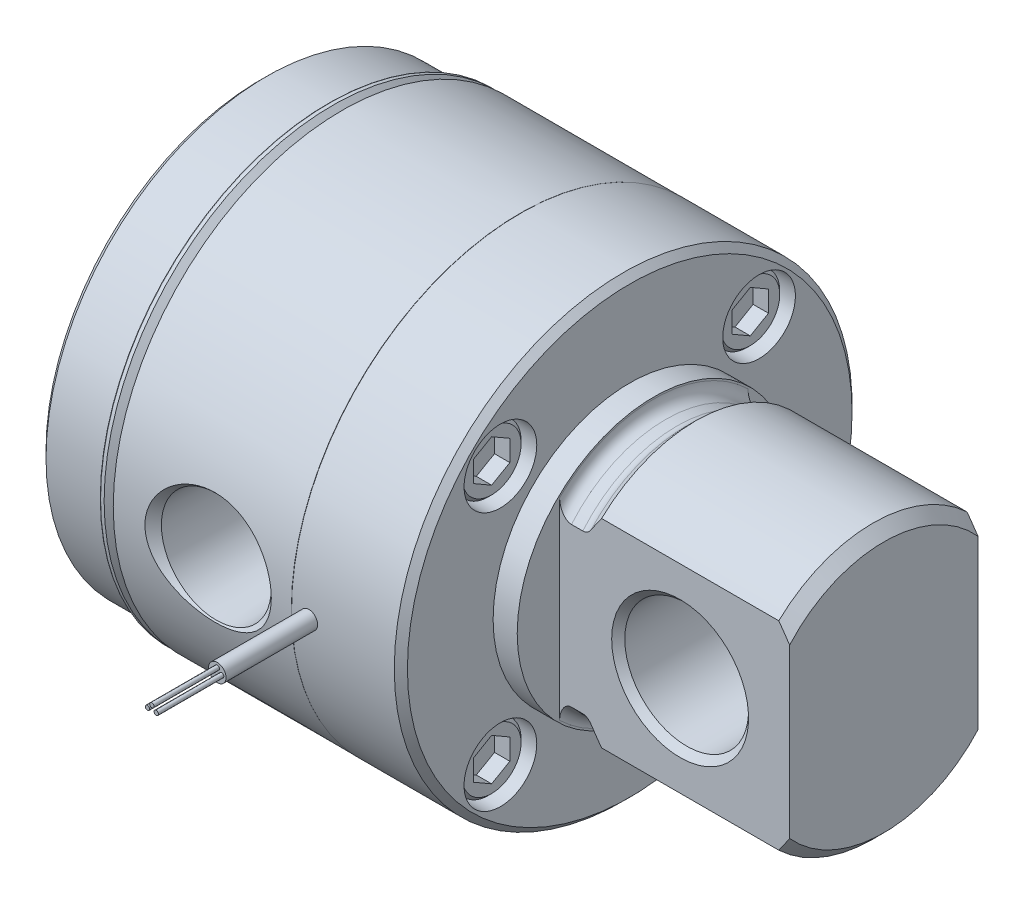
SolidWorks part; units mm, degrees
ref_plane "Front Plane" through (0, 0, 0) normal (0, 0, 1) x (1, 0, 0)
ref_plane "Top Plane" through (0, 0, 0) normal (0, 1, 0) x (1, 0, 0)
ref_plane "Right Plane" through (0, 0, 0) normal (1, 0, 0) x (0, 0, -1)
ref_plane "Plane1" through (0, 0, 0) normal (1, 0, 0) x (0, 0, -1)
sketch "Sketch1" plane through (0, 0, 0) normal (0, 0, 1) x (1, 0, 0)
  line L0 (-42.8752, 0) -> (-42.8752, 24.8158)
  line L1 (-42.8752, 24.8158) -> (-42.1132, 25.5778)
  line L2 (-42.1132, 25.5778) -> (-35.4838, 25.5778)
  line L3 (-35.4838, 25.5778) -> (-34.417, 24.511)
  line L4 (-34.417, 24.511) -> (-33.3502, 24.511)
  line L5 (-33.3502, 24.511) -> (-33.3502, 26.543)
  line L6 (-33.3502, 26.543) -> (-12.7127, 26.5303)
  line L7 (-12.7127, 26.5303) -> (-12.6746, 26.543)
  line L8 (-12.6746, 26.543) -> (-0.762, 26.543)
  line L9 (-0.762, 26.543) -> (0, 25.781)
  line L10 (0, 25.781) -> (0, 0)
  line L11 (0, 0) -> (-42.8752, 0)
  line L12 (0, 0) -> (-42.8752, 0) construction
revolve "Revolve1" add sketch "Sketch1" angle 360 about L12 reverse direction yes
sketch "Sketch2" plane through (0, 0, 0) normal (0, 0, 1) x (1, 0, 0)
  line L0 (-34.9316, 26.3188) -> (-32.8006, 24.1877)
  line L1 (-32.8006, 24.1877) -> (-32.4773, 24.511)
  line L2 (-32.4773, 24.511) -> (-34.4585, 26.4922)
  line L3 (-34.4585, 26.4922) -> (-34.8598, 26.4922)
  line L4 (-34.4585, 0) -> (-35.105, 0) construction
  arc A0 (-34.8598, 26.4922) -> (-34.9316, 26.3188) centre (-34.8598, 26.3906) ccw
revolve "Revolve2" add sketch "Sketch2" angle 360 about L4 reverse direction yes
ref_plane "Plane2" through (0, 0, 0) normal (1, 0, 0) x (0, 0, -1)
hole_wizard "Hole1" positions "Sketch4" profile "Sketch3" legacy
sketch "Sketch4" plane through (0, 0, 0) normal (1, 0, 0) x (0, 0, -1)
  point P0 (-14.997, 14.997)
sketch "Sketch3" plane through (0, 14.997, 14.997) normal (0, 1, 0) x (0, 0, -1)
  line L0 (0, 0) -> (0, 5.08)
  line L1 (0, 5.08) -> (4.2164, 5.08)
  line L2 (4.2164, 5.08) -> (4.2164, 0)
  line L3 (4.2164, 0) -> (0, 0)
  line L4 (0, 110) -> (0, -10) construction
  dimension "Diameter" = 8.4328
  dimension "Depth" = 5.08
sketch "Sketch5" plane through (0, 0, 0) normal (1, 0, 0) x (0, 0, -1)
  line L0 (-14.997, 14.997) -> (14.997, 14.997)
  line L1 (-14.997, 14.997) -> (-14.997, -14.997)
pattern_linear "LPattern1" count 2 spacing 29.9941 along (0, 0, -1) count 2 spacing 29.9941 along (0, -1, 0) of "Hole1"
ref_plane "Plane3" through (0, 0, 0) normal (0, -0.7071, 0.7071) x (1, 0, 0)
sketch "Sketch6" plane through (0, 0, 0) normal (0, -0.7071, 0.7071) x (1, 0, 0)
  line L0 (-5.08, 21.209) -> (-5.08, 25.0038)
  line L1 (-5.08, 25.0038) -> (-1.397, 25.0038)
  line L2 (-1.397, 25.0038) -> (-1.016, 24.6228)
  line L3 (-1.016, 24.6228) -> (-1.016, 21.209)
  line L4 (-1.016, 21.209) -> (-5.08, 21.209)
  line L5 (-1.016, 21.209) -> (-5.08, 21.209) construction
revolve "Revolve3" add sketch "Sketch6" angle 360 about L5 reverse direction yes
sketch "Sketch7" plane through (0, 0, 0) normal (1, 0, 0) x (0, 0, -1)
  line L0 (-14.997, 14.997) -> (14.997, 14.997)
  line L1 (-14.997, 14.997) -> (-14.997, -14.997)
pattern_linear "LPattern2" count 2 spacing 29.9941 along (0, 0, -1) count 2 spacing 29.9941 along (0, -1, 0) of "Revolve3"
ref_plane "Plane4" through (-1.016, 0, 0) normal (1, 0, 0) x (0, 0, -1)
sketch "Sketch8" plane through (-1.016, 0, 0) normal (1, 0, 0) x (0, 0, -1)
  line L0 (-17.1052, 16.2142) -> (-17.1052, 13.7799)
  line L1 (-17.1052, 13.7799) -> (-14.997, 12.5627)
  line L2 (-14.997, 12.5627) -> (-12.8888, 13.7799)
  line L3 (-12.8888, 13.7799) -> (-12.8888, 16.2142)
  line L4 (-12.8888, 16.2142) -> (-14.997, 17.4314)
  line L5 (-14.997, 17.4314) -> (-17.1052, 16.2142)
extrude "Cut-Extrude1" cut sketch "Sketch8" against normal blind 1.778
sketch "Sketch9" plane through (-1.016, 0, 0) normal (1, 0, 0) x (0, 0, -1)
  line L0 (-14.997, 14.997) -> (14.997, 14.997)
  line L1 (-14.997, 14.997) -> (-14.997, -14.997)
pattern_linear "LPattern3" count 2 spacing 29.9941 along (0, 0, -1) count 2 spacing 29.9941 along (0, -1, 0) of "Cut-Extrude1"
sketch "Sketch10" plane through (0, 0, 0) normal (0, 1, 0) x (1, 0, 0)
  line L0 (-10.668, -23.8887) -> (-9.652, -23.8887)
  line L1 (-9.652, -23.8887) -> (-9.652, -37.1602)
  line L2 (-9.652, -37.1602) -> (-10.668, -37.1602)
  line L3 (-10.668, -37.1602) -> (-10.668, -23.8887)
  line L4 (-10.668, -37.1602) -> (-10.668, -23.8887) construction
ref_plane "Plane5" through (0, 0, 24.6634) normal (0, 0, 1) x (1, 0, 0)
revolve "Revolve4" add sketch "Sketch10" angle 360 about L4 reverse direction yes
sketch "Sketch11" plane through (0, 0, 0) normal (0, 1, 0) x (1, 0, 0)
  line L0 (-11.176, -37.1602) -> (-10.922, -37.1602)
  line L1 (-10.922, -37.1602) -> (-10.922, -44.7439)
  line L2 (-10.922, -44.7439) -> (-11.176, -44.7439)
  line L3 (-11.176, -44.7439) -> (-11.176, -37.1602)
  line L4 (-11.176, -44.7439) -> (-11.176, -37.1602) construction
revolve "Revolve5" add sketch "Sketch11" angle 360 about L4 reverse direction yes
sketch "Sketch12" plane through (0, 0, 0) normal (0, 1, 0) x (1, 0, 0)
  line L0 (-10.16, -37.1602) -> (-9.906, -37.1602)
  line L1 (-9.906, -37.1602) -> (-9.906, -44.7439)
  line L2 (-9.906, -44.7439) -> (-10.16, -44.7439)
  line L3 (-10.16, -44.7439) -> (-10.16, -37.1602)
  line L4 (-10.16, -44.7439) -> (-10.16, -37.1602) construction
revolve "Revolve6" add sketch "Sketch12" angle 360 about L4 reverse direction yes
ref_plane "Plane6" through (-10.668, 0, 0) normal (1, 0, 0) x (0, 0, -1)
sketch "Sketch13" plane through (-10.668, 0, 0) normal (1, 0, 0) x (0, 0, -1)
  line L0 (-44.7439, 0.508) -> (-44.7439, 0.762)
  line L1 (-44.7439, 0.762) -> (-37.1602, 0.762)
  line L2 (-37.1602, 0.762) -> (-37.1602, 0.508)
  line L3 (-37.1602, 0.508) -> (-44.7439, 0.508)
  line L4 (-37.1602, 0.508) -> (-44.7439, 0.508) construction
revolve "Revolve7" add sketch "Sketch13" angle 360 about L4 reverse direction yes
sketch "Sketch14" plane through (0, 0, 0) normal (0, 0, 1) x (1, 0, 0)
  line L0 (-42.8752, 0) -> (-42.8752, 13.1699)
  line L1 (-42.8752, 13.1699) -> (-33.7058, 13.1699)
  line L2 (-33.7058, 13.1699) -> (-33.7058, 3.81)
  line L3 (-33.7058, 3.81) -> (-12.7, 3.81)
  line L4 (-12.7, 3.81) -> (-12.7, 12.7)
  line L5 (-12.7, 12.7) -> (-5.08, 12.7)
  line L6 (-5.08, 12.7) -> (-5.08, 0)
  line L7 (-5.08, 0) -> (-42.8752, 0)
  line L8 (-5.08, 0) -> (-42.8752, 0) construction
revolve "Cut-Revolve1" cut sketch "Sketch14" angle 360 about L8 reverse direction yes
sketch "Sketch15" plane through (0, 0, 0) normal (0, 1, 0) x (1, 0, 0)
  line L0 (-22.352, 0) -> (-16.6716, -3.2796)
  line L1 (-16.6716, -3.2796) -> (-16.6716, -3.429)
  line L2 (-16.6716, -3.429) -> (-15.9799, -25.5856)
  line L3 (-15.9799, -25.5856) -> (-15.0225, -26.543)
  line L4 (-15.0225, -26.543) -> (-22.352, -26.543)
  line L5 (-22.352, -26.543) -> (-22.352, 0)
  line L6 (-22.352, -26.543) -> (-22.352, 0) construction
revolve "Cut-Revolve2" cut sketch "Sketch15" angle 360 about L6 reverse direction yes
cosmetic thread "Cosmetic Thread1" parameters "D1"=20.574, "D2"=40.1763
sketch "Sketch16" plane through (0, 0, 0) normal (0, 0, 1) x (1, 0, 0)
  line L0 (0, 0) -> (0, 15.8432)
  line L1 (0, 15.8432) -> (2.794, 15.8432)
  line L2 (2.794, 15.8432) -> (2.794, 15.6337)
  line L3 (4.1656, 14.2621) -> (5.4771, 14.2621)
  line L4 (6.4469, 14.6638) -> (7.6581, 15.875)
  line L5 (7.6581, 15.875) -> (28.2042, 15.875)
  line L6 (28.2042, 15.875) -> (29.464, 14.6152)
  line L7 (29.464, 14.6152) -> (29.464, 0)
  line L8 (29.464, 0) -> (0, 0)
  line L9 (29.464, 0) -> (0, 0) construction
  arc A0 (2.794, 15.6337) -> (4.1656, 14.2621) centre (4.1656, 15.6337) ccw
  arc A1 (5.4771, 14.2621) -> (6.4469, 14.6638) centre (5.4771, 15.6337) ccw
revolve "Revolve8" add sketch "Sketch16" angle 360 about L9 reverse direction yes
cosmetic thread "Cosmetic Thread2" parameters "D1"=23.0171, "D2"=29.2303
ref_plane "Plane7" through (2.794, 0, 0) normal (1, 0, 0) x (0, 0, -1)
sketch "Sketch17" plane through (2.794, 0, 0) normal (1, 0, 0) x (0, 0, -1)
  line L0 (-26.543, -53.086) -> (26.543, -53.086)
  line L1 (26.543, -53.086) -> (26.543, 53.086)
  line L2 (26.543, 53.086) -> (-26.543, 53.086)
  line L3 (-26.543, 53.086) -> (-26.543, -53.086)
  line L4 (-10.922, -26.543) -> (10.922, -26.543)
  line L5 (10.922, -26.543) -> (10.922, 26.543)
  line L6 (10.922, 26.543) -> (-10.922, 26.543)
  line L7 (-10.922, 26.543) -> (-10.922, -26.543)
extrude "Cut-Extrude2" cut sketch "Sketch17" along normal blind 29.464
sketch "Sketch18" plane through (0, 0, 0) normal (0, 1, 0) x (1, 0, 0)
  line L0 (16.764, 10.922) -> (24.7015, 10.922)
  line L1 (24.7015, 10.922) -> (23.9395, 10.16)
  line L2 (23.9395, 10.16) -> (23.9395, -10.16)
  line L3 (23.9395, -10.16) -> (24.7015, -10.922)
  line L4 (24.7015, -10.922) -> (16.764, -10.922)
  line L5 (16.764, -10.922) -> (16.764, 10.922)
  line L6 (16.764, -10.922) -> (16.764, 10.922) construction
revolve "Cut-Revolve3" cut sketch "Sketch18" angle 360 about L6 reverse direction yes
ref_plane "Plane8" through (-42.8752, 0, 0) normal (1, 0, 0) x (0, 0, -1)
ref_plane "Plane9" through (0, 0, 0) normal (0, 0, 1) x (1, 0, 0)
ref_plane "Plane10" through (0, 0, 0) normal (0, 0, 1) x (1, 0, 0)
ref_plane "Plane11" through (0, 0, 0) normal (1, 0, 0) x (0, 0, -1)
ref_plane "Plane12" through (0, 0, 33.655) normal (0, 0, 1) x (1, 0, 0)
ref_plane "Plane13" through (0, -26.543, 0) normal (0, 1, 0) x (1, 0, 0)
ref_plane "IP1 XY" through (0, 0, 0) normal (1, 0, 0) x (0, 0, -1)
ref_plane "IP1 XZ" through (0, 0, 0) normal (0, -1, 0) x (-1, 0, 0)
ref_plane "IP1 YZ" through (0, 0, 0) normal (0, 0, -1) x (-1, 0, 0)
ref_axis "IP1 X" through (0, 0, 80.9) along (0, 0, -1)
ref_axis "IP1 Y" through (0, -50, 0) along (0, 1, 0)
ref_axis "IP1 Z" through (80.9, 0, 0) along (-1, 0, 0)
sketch3d "IP1"
  point P0 (0, 0, 0)
ref_plane "a+stroke XY" through (0, 0, 0) normal (0, 0, 1) x (1, 0, 0)
ref_plane "a+stroke XZ" through (0, 0, 0) normal (0, -1, 0) x (-1, 0, 0)
ref_plane "a+stroke YZ" through (0, 0, 0) normal (1, 0, 0) x (0, 0, -1)
ref_axis "a+stroke X" through (-80.9, 0, 0) along (1, 0, 0)
ref_axis "a+stroke Y" through (0, -50, 0) along (0, 1, 0)
ref_axis "a+stroke Z" through (0, 0, 80.9) along (0, 0, -1)
sketch3d "a+stroke"
  point P0 (0, 0, 0)
ref_plane "d1 XY" through (0, 0, 0) normal (1, 0, 0) x (0, 0, -1)
ref_plane "d1 XZ" through (0, 0, 0) normal (0, -1, 0) x (-1, 0, 0)
ref_plane "d1 YZ" through (0, 0, 26.543) normal (0, 0, -1) x (-1, 0, 0)
ref_axis "d1 X" through (0, 0, 80.9) along (0, 0, -1)
ref_axis "d1 Y" through (0, -50, 26.543) along (0, 1, 0)
ref_axis "d1 Z" through (80.9, 0, 26.543) along (-1, 0, 0)
sketch3d "d1"
  point P0 (0, 0, 26.543)
ref_plane "d2 XY" through (0, 0, 0) normal (1, 0, 0) x (0, 0, -1)
ref_plane "d2 XZ" through (0, 0, 0) normal (0, -1, 0) x (-1, 0, 0)
ref_plane "d2 YZ" through (0, 0, -26.543) normal (0, 0, -1) x (-1, 0, 0)
ref_axis "d2 X" through (0, 0, 80.9) along (0, 0, -1)
ref_axis "d2 Y" through (0, -50, -26.543) along (0, 1, 0)
ref_axis "d2 Z" through (80.9, 0, -26.543) along (-1, 0, 0)
sketch3d "d2"
  point P0 (0, 0, -26.543)
ref_plane "ff1 XY" through (0, 0, 0) normal (1, 0, 0) x (0, 0, -1)
ref_plane "ff1 XZ" through (0, 0, 0) normal (0, -1, 0) x (-1, 0, 0)
ref_plane "ff1 YZ" through (0, 0, 26.543) normal (0, 0, -1) x (-1, 0, 0)
ref_axis "ff1 X" through (0, 0, 80.9) along (0, 0, -1)
ref_axis "ff1 Y" through (0, -50, 26.543) along (0, 1, 0)
ref_axis "ff1 Z" through (80.9, 0, 26.543) along (-1, 0, 0)
sketch3d "ff1"
  point P0 (0, 0, 26.543)
ref_plane "ff2 XY" through (0, 0, 0) normal (1, 0, 0) x (0, 0, -1)
ref_plane "ff2 XZ" through (0, 0, 0) normal (0, -1, 0) x (-1, 0, 0)
ref_plane "ff2 YZ" through (0, 0, 36.195) normal (0, 0, -1) x (-1, 0, 0)
ref_axis "ff2 X" through (0, 0, 80.9) along (0, 0, -1)
ref_axis "ff2 Y" through (0, -50, 36.195) along (0, 1, 0)
ref_axis "ff2 Z" through (80.9, 0, 36.195) along (-1, 0, 0)
sketch3d "ff2"
  point P0 (0, 0, 36.195)
ref_plane "h1 XY" through (0, 0, 0) normal (0, 0, 1) x (1, 0, 0)
ref_plane "h1 XZ" through (0, 0, 0) normal (0, -1, 0) x (-1, 0, 0)
ref_plane "h1 YZ" through (2.794, 0, 0) normal (1, 0, 0) x (0, 0, -1)
ref_axis "h1 X" through (-80.9, 0, 0) along (1, 0, 0)
ref_axis "h1 Y" through (2.794, -50, 0) along (0, 1, 0)
ref_axis "h1 Z" through (2.794, 0, 80.9) along (0, 0, -1)
sketch3d "h1"
  point P0 (2.794, 0, 0)
ref_plane "k1 XY" through (0, 0, 0) normal (0, 0, 1) x (1, 0, 0)
ref_plane "k1 XZ" through (0, 15.875, 0) normal (0, -1, 0) x (-1, 0, 0)
ref_plane "k1 YZ" through (29.464, 0, 0) normal (1, 0, 0) x (0, 0, -1)
ref_axis "k1 X" through (-80.9, 15.875, 0) along (1, 0, 0)
ref_axis "k1 Y" through (29.464, -50, 0) along (0, 1, 0)
ref_axis "k1 Z" through (29.464, 15.875, 80.9) along (0, 0, -1)
sketch3d "k1"
  point P0 (29.464, 15.875, 0)
ref_plane "k2 XY" through (0, 0, 0) normal (0, 0, 1) x (1, 0, 0)
ref_plane "k2 XZ" through (0, -15.875, 0) normal (0, -1, 0) x (-1, 0, 0)
ref_plane "k2 YZ" through (29.464, 0, 0) normal (1, 0, 0) x (0, 0, -1)
ref_axis "k2 X" through (-80.9, -15.875, 0) along (1, 0, 0)
ref_axis "k2 Y" through (29.464, -50, 0) along (0, 1, 0)
ref_axis "k2 Z" through (29.464, -15.875, 80.9) along (0, 0, -1)
sketch3d "k2"
  point P0 (29.464, -15.875, 0)
ref_plane "l1 XY" through (0, 0, 0) normal (0, 0, 1) x (1, 0, 0)
ref_plane "l1 XZ" through (0, 15.8432, 0) normal (0, -1, 0) x (-1, 0, 0)
ref_plane "l1 YZ" through (2.794, 0, 0) normal (1, 0, 0) x (0, 0, -1)
ref_axis "l1 X" through (-80.9, 15.8432, 0) along (1, 0, 0)
ref_axis "l1 Y" through (2.794, -50, 0) along (0, 1, 0)
ref_axis "l1 Z" through (2.794, 15.8432, 80.9) along (0, 0, -1)
sketch3d "l1"
  point P0 (2.794, 15.8432, 0)
ref_plane "l2 XY" through (0, 0, 0) normal (0, 0, 1) x (1, 0, 0)
ref_plane "l2 XZ" through (0, -15.8432, 0) normal (0, -1, 0) x (-1, 0, 0)
ref_plane "l2 YZ" through (2.794, 0, 0) normal (1, 0, 0) x (0, 0, -1)
ref_axis "l2 X" through (-80.9, -15.8432, 0) along (1, 0, 0)
ref_axis "l2 Y" through (2.794, -50, 0) along (0, 1, 0)
ref_axis "l2 Z" through (2.794, -15.8432, 80.9) along (0, 0, -1)
sketch3d "l2"
  point P0 (2.794, -15.8432, 0)
ref_plane "n1 XY" through (0, 0, 0) normal (0, 0, 1) x (1, 0, 0)
ref_plane "n1 XZ" through (0, 0, 0) normal (0, -1, 0) x (-1, 0, 0)
ref_plane "n1 YZ" through (-10.668, 0, 0) normal (1, 0, 0) x (0, 0, -1)
ref_axis "n1 X" through (-80.9, 0, 0) along (1, 0, 0)
ref_axis "n1 Y" through (-10.668, -50, 0) along (0, 1, 0)
ref_axis "n1 Z" through (-10.668, 0, 80.9) along (0, 0, -1)
sketch3d "n1"
  point P0 (-10.668, 0, 0)
ref_plane "o1 XY" through (0, 0, 0) normal (0, 0, 1) x (1, 0, 0)
ref_plane "o1 XZ" through (0, 0, 0) normal (0, -1, 0) x (-1, 0, 0)
ref_plane "o1 YZ" through (-12.7, 0, 0) normal (1, 0, 0) x (0, 0, -1)
ref_axis "o1 X" through (-80.9, 0, 0) along (1, 0, 0)
ref_axis "o1 Y" through (-12.7, -50, 0) along (0, 1, 0)
ref_axis "o1 Z" through (-12.7, 0, 80.9) along (0, 0, -1)
sketch3d "o1"
  point P0 (-12.7, 0, 0)
ref_plane "o2 XY" through (0, 0, 0) normal (0, 0, 1) x (1, 0, 0)
ref_plane "o2 XZ" through (0, 0, 0) normal (0, -1, 0) x (-1, 0, 0)
ref_plane "o2 YZ" through (0, 0, 0) normal (1, 0, 0) x (0, 0, -1)
ref_axis "o2 X" through (-80.9, 0, 0) along (1, 0, 0)
ref_axis "o2 Y" through (0, -50, 0) along (0, 1, 0)
ref_axis "o2 Z" through (0, 0, 80.9) along (0, 0, -1)
sketch3d "o2"
  point P0 (0, 0, 0)
ref_plane "p1 XY" through (0, 0, 0) normal (0, 0, 1) x (1, 0, 0)
ref_plane "p1 XZ" through (0, 0, 0) normal (0, -1, 0) x (-1, 0, 0)
ref_plane "p1 YZ" through (-22.352, 0, 0) normal (1, 0, 0) x (0, 0, -1)
ref_axis "p1 X" through (-80.9, 0, 0) along (1, 0, 0)
ref_axis "p1 Y" through (-22.352, -50, 0) along (0, 1, 0)
ref_axis "p1 Z" through (-22.352, 0, 80.9) along (0, 0, -1)
sketch3d "p1"
  point P0 (-22.352, 0, 0)
ref_plane "q1 XY" through (2.794, 0, 0) normal (1, 0, 0) x (0, 0, -1)
ref_plane "q1 XZ" through (0, 0, 0) normal (0, -1, 0) x (-1, 0, 0)
ref_plane "q1 YZ" through (0, 0, 10.922) normal (0, 0, -1) x (-1, 0, 0)
ref_axis "q1 X" through (2.794, 0, 80.9) along (0, 0, -1)
ref_axis "q1 Y" through (2.794, -50, 10.922) along (0, 1, 0)
ref_axis "q1 Z" through (80.9, 0, 10.922) along (-1, 0, 0)
sketch3d "q1"
  point P0 (2.794, 0, 10.922)
ref_plane "q2 XY" through (2.794, 0, 0) normal (1, 0, 0) x (0, 0, -1)
ref_plane "q2 XZ" through (0, 0, 0) normal (0, -1, 0) x (-1, 0, 0)
ref_plane "q2 YZ" through (0, 0, -10.922) normal (0, 0, -1) x (-1, 0, 0)
ref_axis "q2 X" through (2.794, 0, 80.9) along (0, 0, -1)
ref_axis "q2 Y" through (2.794, -50, -10.922) along (0, 1, 0)
ref_axis "q2 Z" through (80.9, 0, -10.922) along (-1, 0, 0)
sketch3d "q2"
  point P0 (2.794, 0, -10.922)
ref_plane "r1 XY" through (0, 0, 0) normal (1, 0, 0) x (0, 0, -1)
ref_plane "r1 XZ" through (0, -14.997, 0) normal (0, -1, 0) x (-1, 0, 0)
ref_plane "r1 YZ" through (0, 0, 14.997) normal (0, 0, -1) x (-1, 0, 0)
ref_axis "r1 X" through (0, -14.997, 80.9) along (0, 0, -1)
ref_axis "r1 Y" through (0, -50, 14.997) along (0, 1, 0)
ref_axis "r1 Z" through (80.9, -14.997, 14.997) along (-1, 0, 0)
sketch3d "r1"
  point P0 (0, -14.997, 14.997)
ref_plane "r2 XY" through (0, 0, 0) normal (1, 0, 0) x (0, 0, -1)
ref_plane "r2 XZ" through (0, 14.997, 0) normal (0, -1, 0) x (-1, 0, 0)
ref_plane "r2 YZ" through (0, 0, -14.997) normal (0, 0, -1) x (-1, 0, 0)
ref_axis "r2 X" through (0, 14.997, 80.9) along (0, 0, -1)
ref_axis "r2 Y" through (0, -50, -14.997) along (0, 1, 0)
ref_axis "r2 Z" through (80.9, 14.997, -14.997) along (-1, 0, 0)
sketch3d "r2"
  point P0 (0, 14.997, -14.997)
ref_plane "s1 XY" through (0, 0, 0) normal (0, 0, 1) x (1, 0, 0)
ref_plane "s1 XZ" through (0, 0, 0) normal (0, -1, 0) x (-1, 0, 0)
ref_plane "s1 YZ" through (16.764, 0, 0) normal (1, 0, 0) x (0, 0, -1)
ref_axis "s1 X" through (-80.9, 0, 0) along (1, 0, 0)
ref_axis "s1 Y" through (16.764, -50, 0) along (0, 1, 0)
ref_axis "s1 Z" through (16.764, 0, 80.9) along (0, 0, -1)
sketch3d "s1"
  point P0 (16.764, 0, 0)
ref_plane "to_PCS XY" through (0, -26.543, 0) normal (0, -1, 0) x (-1, 0, 0)
ref_plane "to_PCS XZ" through (0, 0, 0) normal (0, 0, -1) x (-1, 0, 0)
ref_plane "to_PCS YZ" through (178.816, 0, 0) normal (1, 0, 0) x (0, 0, -1)
ref_axis "to_PCS X" through (-80.9, -26.543, 0) along (1, 0, 0)
ref_axis "to_PCS Y" through (178.816, -26.543, -50) along (0, 0, 1)
ref_axis "to_PCS Z" through (178.816, -50, 0) along (0, 1, 0)
sketch3d "to_PCS"
  point P0 (178.816, -26.543, 0)
ref_plane "to_bushing XY" through (0, 0, 0) normal (0, 0, 1) x (1, 0, 0)
ref_plane "to_bushing XZ" through (0, 0, 0) normal (0, -1, 0) x (-1, 0, 0)
ref_plane "to_bushing YZ" through (16.764, 0, 0) normal (1, 0, 0) x (0, 0, -1)
ref_axis "to_bushing X" through (-80.9, 0, 0) along (1, 0, 0)
ref_axis "to_bushing Y" through (16.764, -50, 0) along (0, 1, 0)
ref_axis "to_bushing Z" through (16.764, 0, 80.9) along (0, 0, -1)
sketch3d "to_bushing"
  point P0 (16.764, 0, 0)
ref_plane "to_ft XY" through (0, 0, 0) normal (0, 1, 0) x (1, 0, 0)
ref_plane "to_ft XZ" through (0, 0, 36.957) normal (0, 0, 1) x (1, 0, 0)
ref_plane "to_ft YZ" through (-22.352, 0, 0) normal (1, 0, 0) x (0, 0, -1)
ref_axis "to_ft X" through (-80.9, 0, 36.957) along (1, 0, 0)
ref_axis "to_ft Y" through (-22.352, 0, 50) along (0, 0, -1)
ref_axis "to_ft Z" through (-22.352, 50, 36.957) along (0, -1, 0)
sketch3d "to_ft"
  point P0 (-22.352, 0, 36.957)
ref_plane "to_nut XY" through (0, 0, 0) normal (-1, 0, 0) x (0, 0, 1)
ref_plane "to_nut XZ" through (0, 0, 0) normal (0, 1, 0) x (1, 0, 0)
ref_plane "to_nut YZ" through (0, 0, 0) normal (0, 0, -1) x (-1, 0, 0)
ref_axis "to_nut X" through (0, 0, 80.9) along (0, 0, -1)
ref_axis "to_nut Y" through (0, 50, 0) along (0, -1, 0)
ref_axis "to_nut Z" through (-80.9, 0, 0) along (1, 0, 0)
sketch3d "to_nut"
  point P0 (0, 0, 0)
ref_plane "to_plug_connector XY" through (0, 0, 33.655) normal (0, 0, 1) x (1, 0, 0)
ref_plane "to_plug_connector XZ" through (0, 0, 0) normal (0, -1, 0) x (-1, 0, 0)
ref_plane "to_plug_connector YZ" through (-10.668, 0, 0) normal (1, 0, 0) x (0, 0, -1)
ref_axis "to_plug_connector X" through (-80.9, 0, 33.655) along (1, 0, 0)
ref_axis "to_plug_connector Y" through (-10.668, -50, 33.655) along (0, 1, 0)
ref_axis "to_plug_connector Z" through (-10.668, 0, 80.9) along (0, 0, -1)
sketch3d "to_plug_connector"
  point P0 (-10.668, 0, 33.655)
ref_plane "to_tube XY" through (-42.8752, 0, 0) normal (1, 0, 0) x (0, 0, -1)
ref_plane "to_tube XZ" through (0, 0, 0) normal (0, -1, 0) x (-1, 0, 0)
ref_plane "to_tube YZ" through (0, 0, 0) normal (0, 0, -1) x (-1, 0, 0)
ref_axis "to_tube X" through (-42.8752, 0, 80.9) along (0, 0, -1)
ref_axis "to_tube Y" through (-42.8752, -50, 0) along (0, 1, 0)
ref_axis "to_tube Z" through (80.9, 0, 0) along (-1, 0, 0)
sketch3d "to_tube"
  point P0 (-42.8752, 0, 0)
ref_plane "u XY" through (0, 0, 0) normal (0, 0, 1) x (1, 0, 0)
ref_plane "u XZ" through (0, 0, 0) normal (0, -1, 0) x (-1, 0, 0)
ref_plane "u YZ" through (29.464, 0, 0) normal (1, 0, 0) x (0, 0, -1)
ref_axis "u X" through (-80.9, 0, 0) along (1, 0, 0)
ref_axis "u Y" through (29.464, -50, 0) along (0, 1, 0)
ref_axis "u Z" through (29.464, 0, 80.9) along (0, 0, -1)
sketch3d "u"
  point P0 (29.464, 0, 0)
ref_plane "v1 XY" through (0, 0, 0) normal (0, 0, 1) x (1, 0, 0)
ref_plane "v1 XZ" through (0, 0, 0) normal (0, -1, 0) x (-1, 0, 0)
ref_plane "v1 YZ" through (11.1633, 0, 0) normal (1, 0, 0) x (0, 0, -1)
ref_axis "v1 X" through (-80.9, 0, 0) along (1, 0, 0)
ref_axis "v1 Y" through (11.1633, -50, 0) along (0, 1, 0)
ref_axis "v1 Z" through (11.1633, 0, 80.9) along (0, 0, -1)
sketch3d "v1"
  point P0 (11.1633, 0, 0)
ref_plane "v2 XY" through (0, 0, 0) normal (0, 0, 1) x (1, 0, 0)
ref_plane "v2 XZ" through (0, 0, 0) normal (0, -1, 0) x (-1, 0, 0)
ref_plane "v2 YZ" through (22.3647, 0, 0) normal (1, 0, 0) x (0, 0, -1)
ref_axis "v2 X" through (-80.9, 0, 0) along (1, 0, 0)
ref_axis "v2 Y" through (22.3647, -50, 0) along (0, 1, 0)
ref_axis "v2 Z" through (22.3647, 0, 80.9) along (0, 0, -1)
sketch3d "v2"
  point P0 (22.3647, 0, 0)
